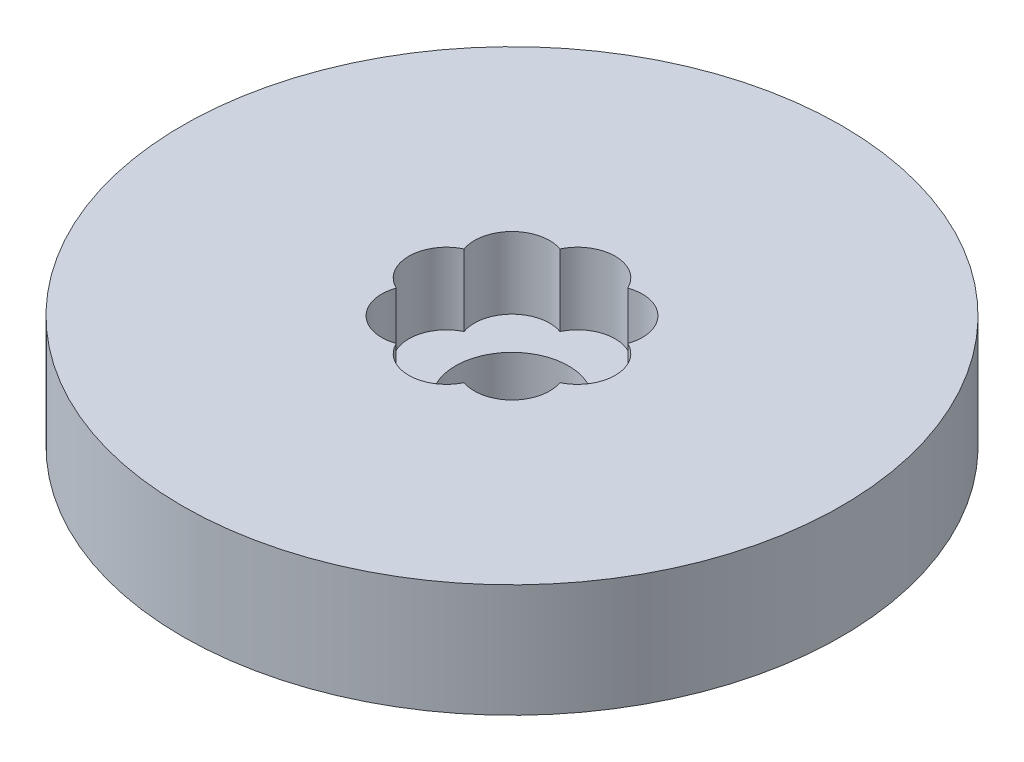
SolidWorks part; units mm, degrees
ref_plane "Front Plane" through (0, 0, 0) normal (0, 0, 1) x (1, 0, 0)
ref_plane "Top Plane" through (0, 0, 0) normal (0, 1, 0) x (1, 0, 0)
ref_plane "Right Plane" through (0, 0, 0) normal (1, 0, 0) x (0, 0, -1)
sketch "Sketch1" plane through (0, 0, 0) normal (0, 1, 0) x (1, 0, 0)
  circle A0 centre (0, 0) radius 87.5
  dimension "FLANGE_OD" = 175
extrude "Boss-Extrude1" add sketch "Sketch1" along normal blind 30
sketch "Sketch2" plane through (0, 0, 0) normal (0, 1, 0) x (1, 0, 0)
  circle A0 centre (0, 0) radius 15
  dimension "BORE_D" = 30
extrude "Cut-Extrude1" cut sketch "Sketch2" along normal through all
sketch "Sketch3" plane through (0, 30, 0) normal (0, 1, 0) x (1, 0, 0)
  circle A0 centre (0, 0) radius 17.4083 construction
  circle A1 centre (-17.4083, 0) radius 10
  dimension "BOLT_D" = 20
  dimension "BOLT_PCD" = 34.8166
extrude "Cut-Extrude2" cut sketch "Sketch3" against normal blind 19.0046
pattern_circular "CirPattern1" count 8 over 360 about axis through (0, 0, 0) along (0, 1, 0) of "Cut-Extrude2"
